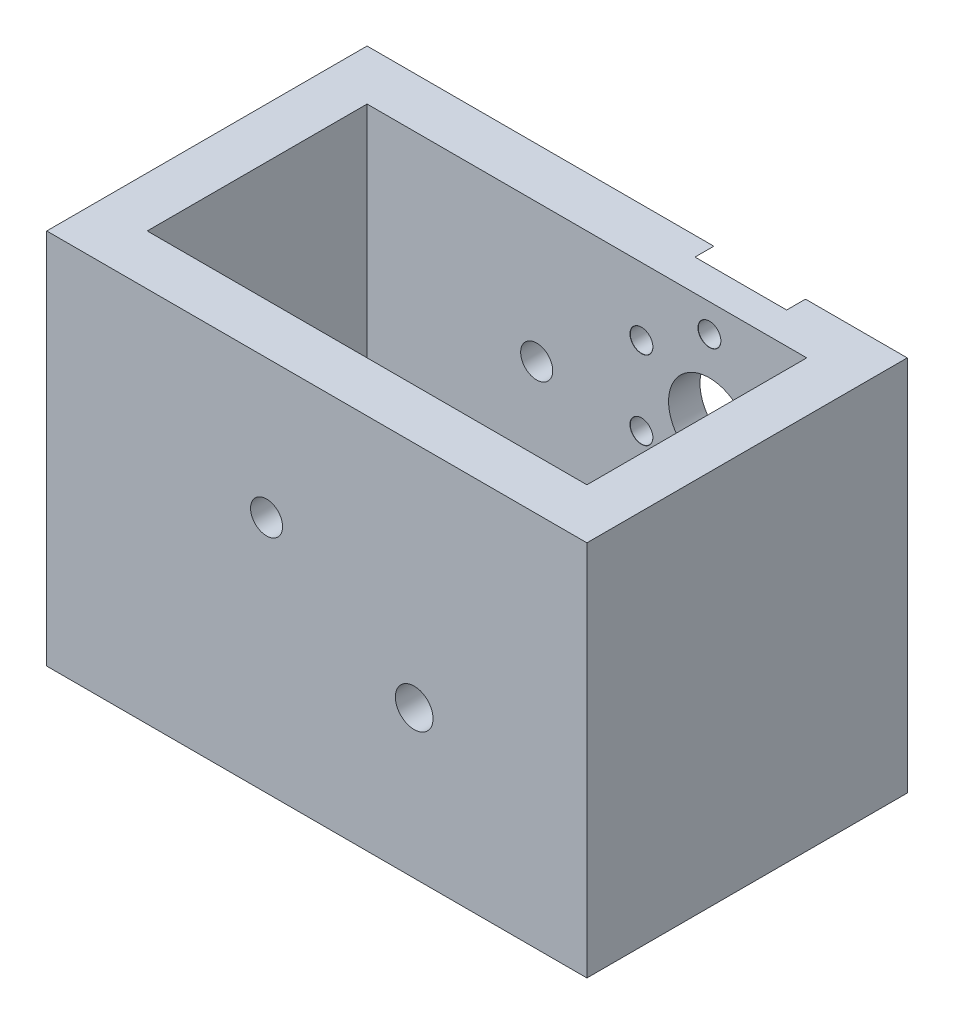
SolidWorks part; units mm, degrees
material "PLA"
ref_plane "Front Plane" through (0, 0, 0) normal (0, 0, 1) x (1, 0, 0)
ref_plane "Top Plane" through (0, 0, 0) normal (0, 1, 0) x (1, 0, 0)
ref_plane "Right Plane" through (0, 0, 0) normal (1, 0, 0) x (0, 0, -1)
sketch "Sketch1" plane through (0, 0, 0) normal (0, 1, 0) x (1, 0, 0)
  line L0 (-35, 0) -> (35, 0)
  line L1 (35, 0) -> (35, -27)
  line L2 (35, -27) -> (43, -27) construction
  line L3 (43, -27) -> (43, 8)
  line L4 (43, 8) -> (-43, 8)
  line L5 (-43, 8) -> (-43, -27)
  line L6 (-43, -27) -> (-35, -27) construction
  line L7 (-35, -27) -> (-35, 0)
  line L8 (-35, 0) -> (-43, 0)
  line L9 (35, 0) -> (43, 0)
  line L10 (-35, -39) -> (-35, 4) construction
  line L11 (-35, 4) -> (35, 4) construction
  line L12 (35, 4) -> (35, -39) construction
  line L13 (-43, -27) -> (-43, -43)
  line L14 (-43, -43) -> (43, -43)
  line L15 (43, -43) -> (43, -27)
  line L16 (35, -27) -> (35, -35)
  line L17 (35, -35) -> (-35, -35)
  line L18 (-35, -35) -> (-35, -27)
  line L19 (-35, -39) -> (33.7816, -39) construction
  point P8 (0, 0)
  point P12 (-35, -39)
  point P13 (35, -39)
  point P14 (35, 4)
  point P15 (-35, 4)
  dimension "D1" = 8
  dimension "D2" = 8
  dimension "D3" = 8
  dimension "D4" = 70
  dimension "D5" = 27
  dimension "D6" = 35
  dimension "D7" = 8
  dimension "D8" = 70
  dimension "D9" = 43
  dimension "D10" = 35
extrude "Boss-Extrude1" add sketch "Sketch1" along normal blind 60 contours L7 L8 L5 L6 | L0 L9 L3 L4 L5 L8 | L9 L1 L2 L3 region at (0, 0, -4) region at (-35.9615, 0, 13.5)
sketch "Sketch4" plane through (0, 0, 0) normal (0, 0, 1) x (1, 0, 0)
  line L1 (-35, 0) -> (35, 0) construction
  line L3 (19.5, 44) -> (19.5, 23.6384) construction
  line L6 (43, 60) -> (43, 0) construction
  circle A0 centre (19.5, 43) radius 12.5 construction
  circle A1 centre (19.5, 43) radius 6.5
  point P0 (19.5, 43)
  point P7 (19.5, 55.5)
  point P11 (30.3253, 49.25)
  point P12 (30.3253, 36.75)
  point P13 (19.5, 30.5)
  point P14 (8.6747, 36.75)
  point P15 (8.6747, 49.25)
  point P16 (19.5, 43)
  dimension "D3" = 25
  dimension "D5" = 13
  dimension "D1" = 23.5
  dimension "D2" = 43
  dimension "D4" = 6
hole_wizard "M3 Clearance Hole1" positions "Sketch5" profile "Sketch6" hole size "M3" standard "ISO" end condition through all
sketch "Sketch5" plane through (0, 0, 0) normal (0, 0, 1) x (1, 0, 0)
  point P0 (19.5, 55.5)
  point P3 (30.3253, 49.25)
  point P6 (30.3253, 36.75)
  point P9 (19.5, 30.5)
  point P12 (8.6747, 36.75)
  point P15 (8.6747, 49.25)
sketch "Sketch6" plane through (19.5, 55.5, 0) normal (1, 0, 0) x (0, -1, 0)
  line L0 (0, 0) -> (0, 8)
  line L1 (0, 8) -> (1.8, 8)
  line L2 (1.8, 8) -> (1.8, 0.025)
  line L3 (1.8, 0.025) -> (1.825, 0)
  line L5 (1.825, 0) -> (0, 0)
  line L6 (-1.8, 0.025) -> (-1.825, 0) construction
  line L11 (0, -6.35) -> (0, 107.95) construction
  dimension "Thru Hole Dia." = 3.6
  dimension "Thru Hole Depth" = 8
  dimension "Near C'Sink Dia." = 3.65
  dimension "Near C'Sink Angle" = 90
extrude "Cut-Extrude1" cut sketch "Sketch4" against normal through all
hole_wizard "Ø5.3 (5.3) Diameter Hole1" positions "Sketch7" profile "Sketch9" hole size "Ø5.3" standard "ISO"
sketch "Sketch7" plane through (0, 0, 0) normal (0, -1, 0) x (-1, 0, 0)
  point P0 (-35, 4)
  point P3 (-35, -39)
  point P6 (35, 4)
  point P9 (35, -39)
sketch "Sketch9" plane through (35, 0, -4) normal (1, 0, 0) x (0, 0, -1)
  line L0 (0, 0) -> (0, 8.5923)
  line L1 (0, 8.5923) -> (2.65, 7)
  line L2 (2.65, 7) -> (2.65, 0)
  line L5 (2.65, 0) -> (0, 0)
  line L10 (0, 8.5923) -> (-2.65, 7) construction
  line L11 (0, -6.35) -> (0, 107.95) construction
  dimension "Hole Dia." = 5.3
  dimension "Hole Depth" = 7
  dimension "Drill Angle" = 118
sketch "Sketch10" plane through (0, 0, 0) normal (0, 0, 1) x (1, 0, 0)
  line L0 (-35, 0) -> (35, 0) construction
  line L1 (43, 60) -> (43, 0) construction
  circle A0 centre (15.5, 23.5) radius 3
  dimension "D2" = 6
  dimension "D1" = 23.5
  dimension "D3" = 27.5
extrude "Cut-Extrude2" cut sketch "Sketch10" against normal through all both and the other way through all
sketch "Sketch11" plane through (0, 0, 0) normal (0, 0, 1) x (1, 0, 0)
  line L2 (-35, 60) -> (35, 60) construction
  line L4 (-43, 60) -> (-43, 0) construction
  circle A0 centre (-8, 38) radius 2.55
  dimension "D1" = 5.1
  dimension "D2" = 35
  dimension "D3" = 22
extrude "Cut-Extrude3" cut sketch "Sketch11" against normal through all both and the other way through all
sketch "Sketch12" plane through (0, 0, -8) normal (0, 0, -1) x (-1, 0, 0)
  circle A0 centre (-19.5, 43) radius 18.5
  circle A1 centre (-19.5, 43) radius 6.5 construction
  dimension "D1" = 37
extrude "Cut-Extrude4" cut sketch "Sketch12" against normal blind 3
